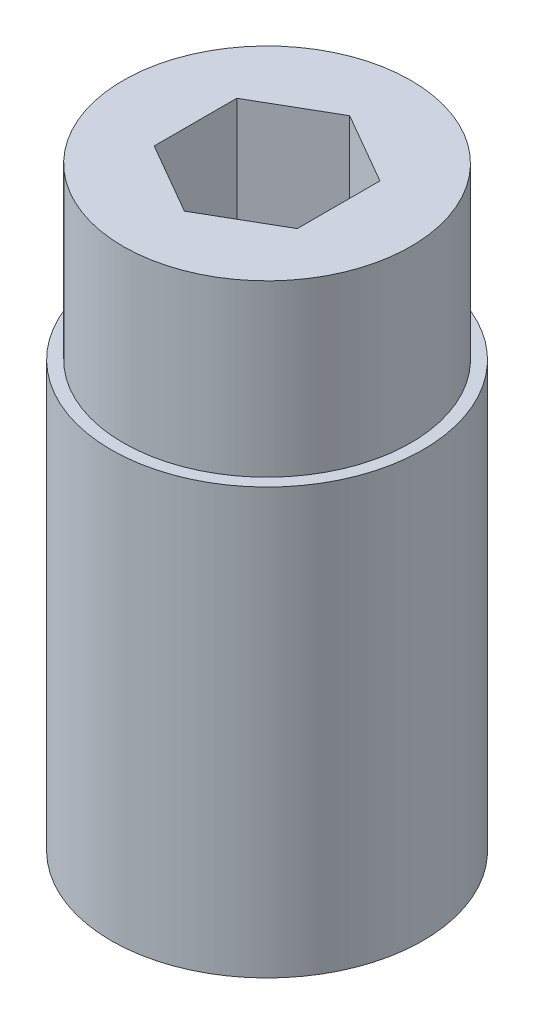
SolidWorks part; units mm, degrees
ref_plane "Front Plane" through (0, 0, 0) normal (0, 0, 1) x (1, 0, 0)
ref_plane "Top Plane" through (0, 0, 0) normal (0, 1, 0) x (1, 0, 0)
ref_plane "Right Plane" through (0, 0, 0) normal (1, 0, 0) x (0, 0, -1)
sketch "Sketch1" plane through (0, 0, 0) normal (0, 1, 0) x (1, 0, 0)
  circle A0 centre (0, 0) radius 7
  dimension "D1" = 14
extrude "Boss-Extrude1" add sketch "Sketch1" along normal blind 15
sketch "Sketch2" plane through (0, 15, 0) normal (0, 1, 0) x (1, 0, 0)
  circle A0 centre (0, 0) radius 5.075
  dimension "D1" = 10.15
extrude "Boss-Extrude2" add sketch "Sketch2" along normal blind 6
sketch "Sketch3" plane through (0, 21, 0) normal (0, 1, 0) x (1, 0, 0)
  line L1 (3.5, -1.4434) -> (3.5, 1.4434)
  line L2 (3.5, 1.4434) -> (1, 2.8868)
  line L3 (1, 2.8868) -> (-1.5, 1.4434)
  line L4 (-1.5, 1.4434) -> (-1.5, -1.4434)
  line L5 (-1.5, -1.4434) -> (1, -2.8868)
  line L6 (1, -2.8868) -> (3.5, -1.4434)
  circle A0 centre (1, 0) radius 2.5 construction
  dimension "D1" = 5
  dimension "D2" = 1
extrude "Cut-Extrude1" [suppressed] cut sketch "Sketch3" against normal through all
sketch "Sketch4" plane through (0, 21, 0) normal (0, 1, 0) x (1, 0, 0)
  line L1 (2.525, 1.4578) -> (0, 2.9156)
  line L2 (0, 2.9156) -> (-2.525, 1.4578)
  line L3 (-2.525, 1.4578) -> (-2.525, -1.4578)
  line L4 (-2.525, -1.4578) -> (0, -2.9156)
  line L5 (0, -2.9156) -> (2.525, -1.4578)
  line L6 (2.525, -1.4578) -> (2.525, 1.4578)
  circle A0 centre (0, 0) radius 2.525 construction
  dimension "D1" = 5.05
extrude "Cut-Extrude2" cut sketch "Sketch4" against normal through all
sketch "Sketch5" plane through (0, 15, 0) normal (0, 1, 0) x (1, 0, 0)
  circle A0 centre (0, 0) radius 5.5
  dimension "D1" = 11
extrude "Cut-Extrude3" cut sketch "Sketch5" against normal through all flip side to cut
equation "\"R_ROLL\"= 5mm"
equation "\"D_SUN\"= 80mm"
equation "\"NUM_ROLL\"= 16"
equation "\"RHO\"= 1mm"
equation "\"D_SHAFT\"= 15mm"
equation "\"D_OUTPUT\"= 40mm"
equation "\"NUM_OUT\"= 6"
equation "\"R_OUT_ROLL\"= 5mm"
